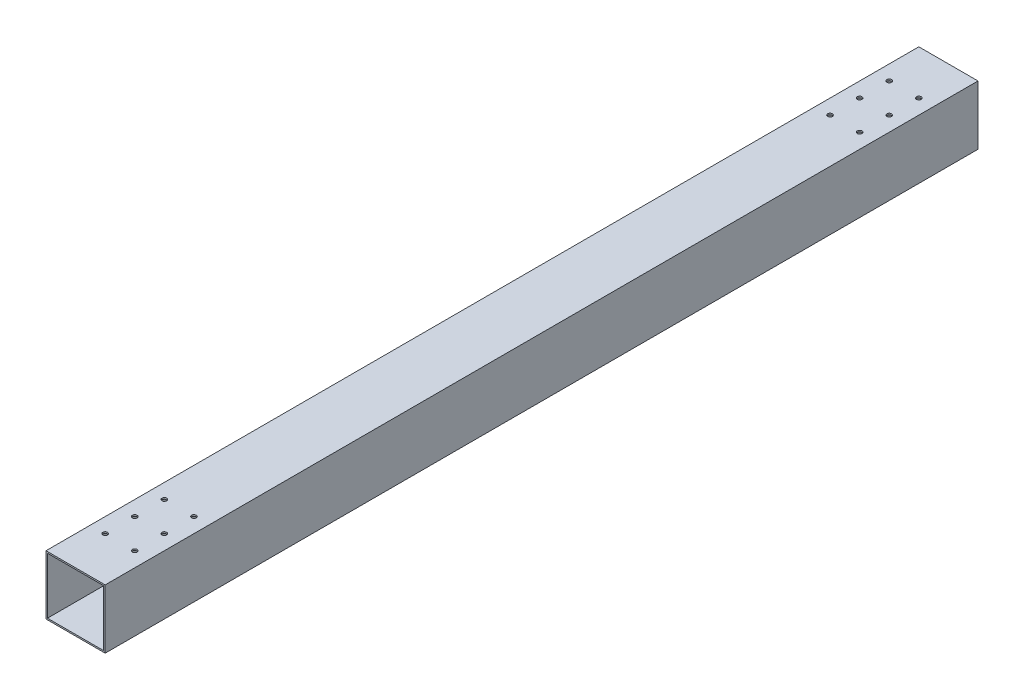
SolidWorks part; units mm, degrees
material "6061 合金"
ref_plane "前视基准面" through (0, 0, 0) normal (0, 0, 1) x (1, 0, 0)
ref_plane "上视基准面" through (0, 0, 0) normal (0, 1, 0) x (1, 0, 0)
ref_plane "右视基准面" through (0, 0, 0) normal (1, 0, 0) x (0, 0, -1)
other "Configuration Table"
sketch "草图1" plane through (0, 0, 0) normal (0, 0, 1) x (1, 0, 0)
  line L1 (-20, 20) -> (20, 20)
  line L2 (-20, 20) -> (-20, -20)
  line L3 (-20, -20) -> (20, -20)
  line L4 (20, 20) -> (20, -20)
  line L5 (-20, 20) -> (20, -20) construction
  line L6 (-20, -20) -> (20, 20) construction
  line L7 (-19, 19) -> (19, 19)
  line L8 (-19, 19) -> (-19, -19)
  line L9 (-19, -19) -> (19, -19)
  line L10 (19, 19) -> (19, -19)
  line L11 (-19, 19) -> (19, -19) construction
  line L12 (-19, -19) -> (19, 19) construction
  point P0 (0, 0)
  point P6 (0, 0)
  dimension "D1" = 40
  dimension "D2" = 1
extrude "凸台-拉伸1" add sketch "草图1" along normal mid plane 590
sketch "草图2" plane through (0, 20, 0) normal (0, 1, 0) x (1, 0, 0)
  line L0 (0, -290) -> (0, -50290) construction
  line L1 (20, -295) -> (-20, -295) construction
  line L2 (-10, -167.5) -> (-10, -147.5) construction
  line L3 (0, 0) -> (50000, 0) construction
  circle A0 centre (-10, -167.5) radius 1.6
  circle A1 centre (10, -167.5) radius 1.6
  circle A2 centre (-10, -147.5) radius 1.6
  circle A3 centre (10, -147.5) radius 1.6
  circle A4 centre (-10, -127.5) radius 1.6
  circle A5 centre (10, -127.5) radius 1.6
  circle A6 centre (-10, -107.5) radius 1.6
  circle A7 centre (10, -107.5) radius 1.6
  circle A8 centre (10, 107.5) radius 1.6
  circle A9 centre (-10, 107.5) radius 1.6
  circle A10 centre (10, 127.5) radius 1.6
  circle A11 centre (-10, 127.5) radius 1.6
  circle A12 centre (10, 147.5) radius 1.6
  circle A13 centre (-10, 147.5) radius 1.6
  circle A14 centre (10, 167.5) radius 1.6
  circle A15 centre (-10, 167.5) radius 1.6
  point P4 (0, -295)
  dimension "D1" = 20
  dimension "D2" = 3.2
  dimension "D3" = 107.5
  dimension "D5" = 20
  dimension "D4" = 4
sketch "草图3" plane through (0, 20, 0) normal (0, 1, 0) x (1, 0, 0)
  circle A0 centre (-10, 225) radius 1.6 construction
  circle A1 centre (10, 225) radius 1.6 construction
  circle A2 centre (10, 245) radius 1.6 construction
  circle A3 centre (-10, 245) radius 1.6 construction
  circle A4 centre (-10, 265) radius 1.6 construction
  circle A5 centre (10, 265) radius 1.6 construction
  circle A6 centre (-10, 225) radius 1.6
  circle A7 centre (10, 225) radius 1.6
  circle A8 centre (10, 245) radius 1.6
  circle A9 centre (-10, 245) radius 1.6
  circle A10 centre (-10, 265) radius 1.6
  circle A11 centre (10, 265) radius 1.6
  circle A12 centre (10, -265) radius 1.6 construction
  circle A13 centre (-10, -265) radius 1.6 construction
  circle A14 centre (-10, -245) radius 1.6 construction
  circle A15 centre (10, -245) radius 1.6 construction
  circle A16 centre (10, -225) radius 1.6 construction
  circle A17 centre (-10, -225) radius 1.6 construction
  circle A18 centre (10, -265) radius 1.6
  circle A19 centre (-10, -265) radius 1.6
  circle A20 centre (-10, -245) radius 1.6
  circle A21 centre (10, -245) radius 1.6
  circle A22 centre (10, -225) radius 1.6
  circle A23 centre (-10, -225) radius 1.6
extrude "切除-拉伸2" cut sketch "草图3" against normal up to next
